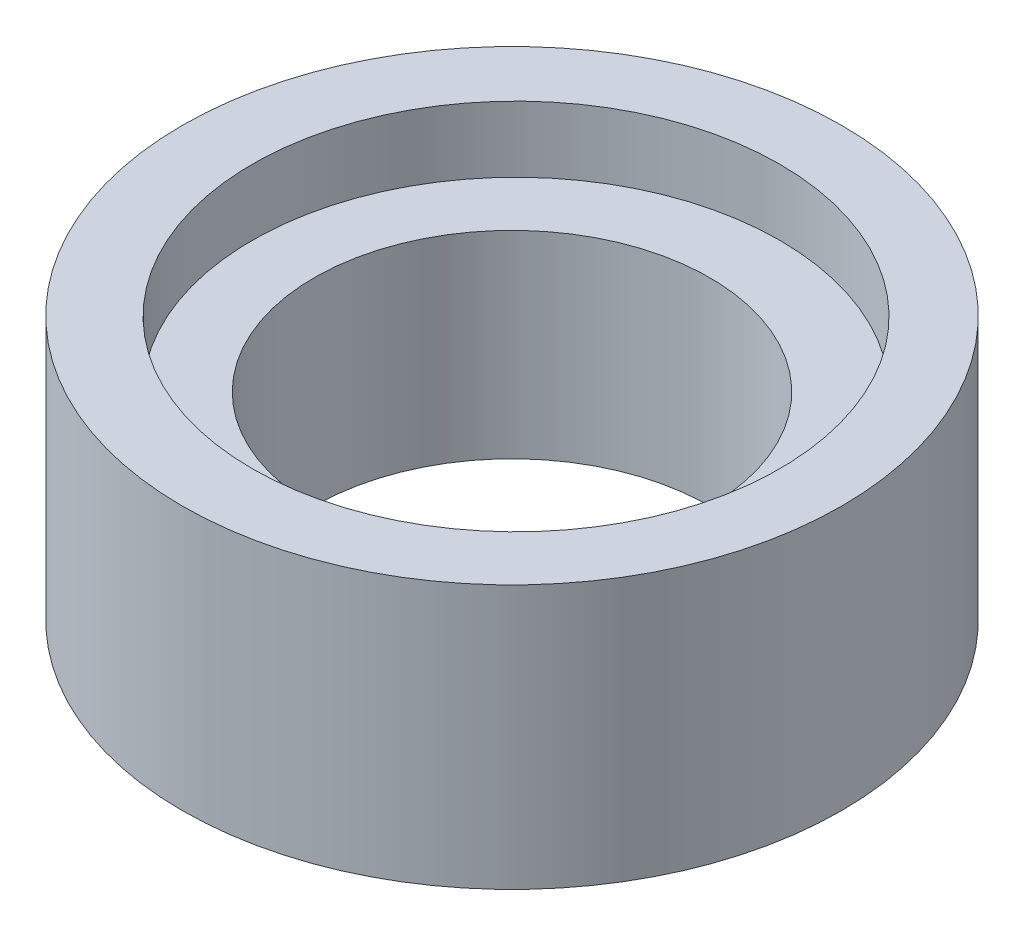
SolidWorks part; units mm, degrees
ref_plane "Front Plane" through (0, 0, 0) normal (0, 0, 1) x (1, 0, 0)
ref_plane "Top Plane" through (0, 0, 0) normal (0, 1, 0) x (1, 0, 0)
ref_plane "Right Plane" through (0, 0, 0) normal (1, 0, 0) x (0, 0, -1)
sketch "Sketch1" plane through (0, 0, 0) normal (0, 1, 0) x (1, 0, 0)
  circle A1 centre (0, 0) radius 25
  dimension "D1" = 50
extrude "Boss-Extrude5" add sketch "Sketch1" along normal blind 20
sketch "Sketch5" plane through (0, 20, 0) normal (0, 1, 0) x (1, 0, 0)
  circle A0 centre (0.2024, 0.1044) radius 0.2278
  circle A2 centre (0.2024, 0.1044) radius 20
extrude "Cut-Extrude2" cut sketch "Sketch5" against normal blind 5 and the other way blind 1 contours A2
sketch "Sketch9" plane through (0, 15, 0) normal (0, 1, 0) x (1, 0, 0)
  circle A0 centre (0, 0) radius 15
extrude "Cut-Extrude3" cut sketch "Sketch9" against normal blind 29 contours A0
ref_axis "Axis3" through (0, 20, 0) along (0, -1, 0)
